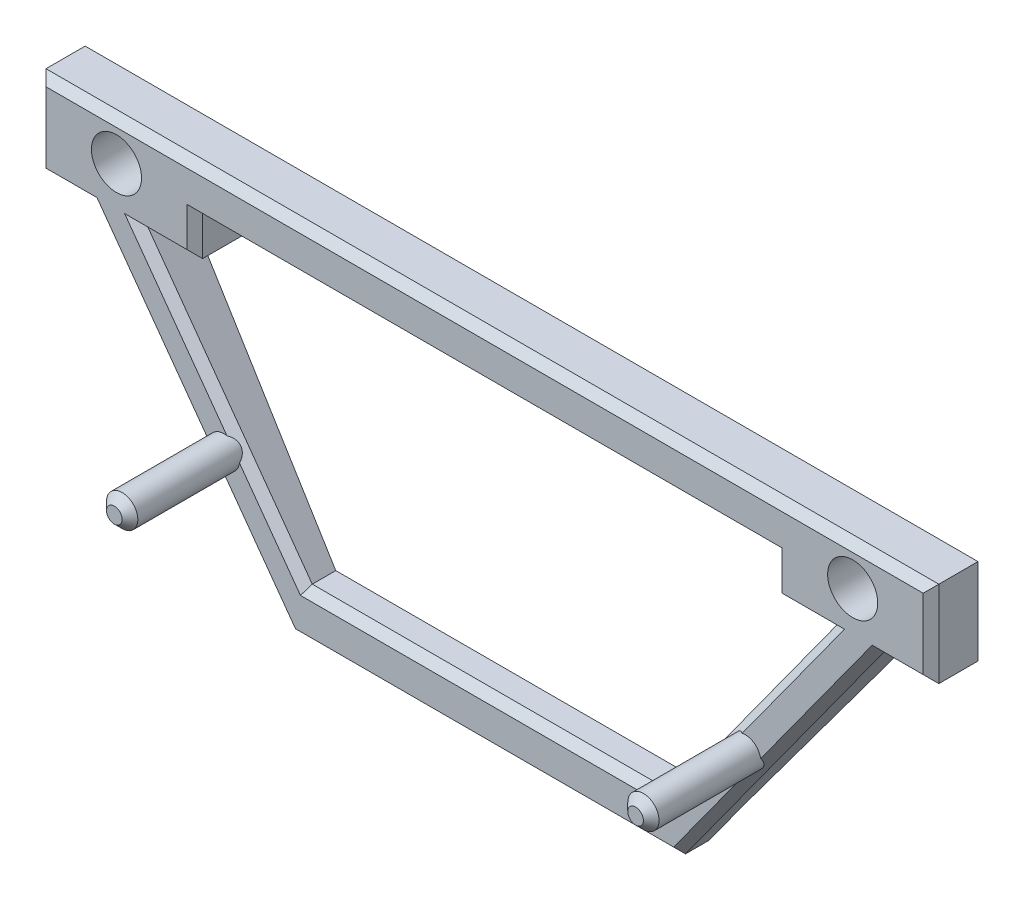
SolidWorks part; units mm, degrees
ref_plane "Ebene vorne" through (0, 0, 0) normal (0, 0, 1) x (1, 0, 0)
ref_plane "Ebene oben" through (0, 0, 0) normal (0, 1, 0) x (1, 0, 0)
ref_plane "Ebene rechts" through (0, 0, 0) normal (1, 0, 0) x (0, 0, -1)
sketch "Skizze1" plane through (0, 0, 0) normal (0, 0, 1) x (1, 0, 0)
  line L0 (0, 0) -> (0, 46.9928) construction
  line L3 (28.5, 17.5) -> (28.5, 23)
  line L5 (18.5, 20) -> (18.5, 17.5)
  line L13 (18.5, 17.5) -> (22, 17.5)
  line L14 (28.5, 17.5) -> (25, 17.5)
  line L15 (22, 17.5) -> (11.5, 3)
  line L16 (25, 17.5) -> (12.3276, 0)
  line L17 (11.5, 3) -> (-11.5, 3)
  line L18 (12.3276, 0) -> (-12.3276, 0)
  line L19 (-25, 17.5) -> (-12.3276, 0)
  line L20 (-22, 17.5) -> (-11.5, 3)
  line L21 (-28.5, 17.5) -> (-25, 17.5)
  line L22 (-18.5, 17.5) -> (-22, 17.5)
  line L23 (-18.5, 20) -> (-18.5, 17.5)
  line L24 (-28.5, 23) -> (28.5, 23)
  line L25 (-28.5, 17.5) -> (-28.5, 23)
  line L26 (22.5, 18.75) -> (22.5, 4.6099) construction
  line L28 (-18.5, 20) -> (18.5, 20)
  point P9 (0, 3)
  point P12 (0, 3)
  point P26 (28.5, 20.25)
  dimension "D1" = 23
  dimension "D2" = 57
  dimension "D3" = 5.5
  dimension "D4" = 3
  dimension "D5" = 3
  dimension "D6" = 3.5
  dimension "D7" = 10
  dimension "D8" = 3
  dimension "D9" = 23
extrude "Aufsatz-Linear austragen1" add sketch "Skizze1" along normal blind 3
sketch "Skizze3" plane through (0, 0, 3) normal (0, 0, 1) x (1, 0, 0)
  line L0 (0, 0) -> (0, 62.4514) construction
  line L1 (23.5, 17.5) -> (23.5, 34.1584) construction
  line L2 (25, 17.5) -> (28.5, 17.5) construction
  line L3 (28.5, 17.5) -> (28.5, 23) construction
  line L5 (-23.5, 17.5) -> (-23.5, 34.1584) construction
  circle A0 centre (23.5, 20.5) radius 1.6
  circle A1 centre (-23.5, 20.5) radius 1.6
  dimension "D2" = 3.2
  dimension "D1" = 5
  dimension "D3" = 3
extrude "Bohrungen" cut sketch "Skizze3" against normal through all
sketch "Skizze4" plane through (28.5, 0, 0) normal (1, 0, 0) x (0, 0, -1)
  line L1 (0, 17.5) -> (-1, 3)
  line L6 (-1, 3) -> (-1, 0)
  line L7 (-3, 0) -> (0, 0) construction
  line L8 (-1, 0) -> (0, 0)
  line L9 (0, 0) -> (0, 17.5)
  dimension "D1" = 1
  dimension "D2" = 3
extrude "Dicken_anpassung" cut sketch "Skizze4" against normal through all
sketch "Skizze5" plane through (0, 0, 3) normal (0, 0, 1) x (1, 0, 0)
  line L0 (0, 0) -> (0, 27.2221) construction
  line L2 (12.3276, 0) -> (25, 17.5) construction
  line L4 (28.5, 23) -> (-28.5, 23) construction
  circle A0 centre (16.6391, 8) radius 1
  circle A2 centre (-16.6391, 8) radius 1
  dimension "D2" = 2
  dimension "D1" = 15
  dimension "D4" = 1.2
extrude "Akkuhalterungen" add sketch "Skizze5" along normal blind 7
chamfer "Fase1" distance 0.5 angle 45 18 edges at (16.75, 10.25, 3) (20.25, 17.5, 3) (18.5, 18.75, 3) (0, 20, 3) (-18.5, 18.75, 3) (-20.25, 17.5, 3) (-16.75, 10.25, 3) (0, 3, 3) (-28.5, 20.25, 3) (0, 23, 3) (28.5, 20.25, 3) (26.75, 17.5, 3) (18.6638, 8.75, 3) (0, 0, 3) (-18.6638, 8.75, 3) (-26.75, 17.5, 3) (-17.6391, 8, 10) (17.6391, 8, 10)
